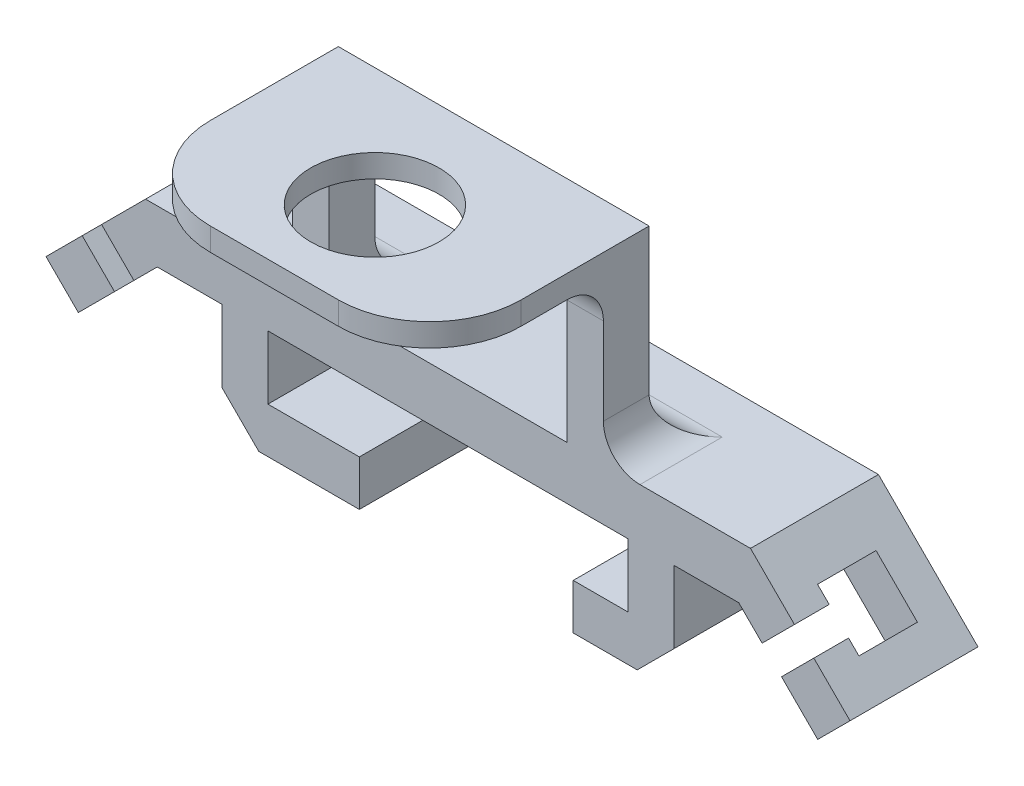
SolidWorks part; units mm, degrees
ref_plane "Front Plane" through (0, 0, 0) normal (0, 0, 1) x (1, 0, 0)
ref_plane "Top Plane" through (0, 0, 0) normal (0, 1, 0) x (1, 0, 0)
ref_plane "Right Plane" through (0, 0, 0) normal (1, 0, 0) x (0, 0, -1)
sketch "Sketch2" plane through (0, 0, 0) normal (0, 0, 1) x (1, 0, 0)
  line L0 (15.9053, 19.45) -> (-15.9053, 19.45)
  line L1 (16.5463, 22.3446) -> (-16.5463, 22.3446)
  line L2 (15.9053, 19.45) -> (20.2233, 15.1321)
  line L5 (20.2233, 15.1321) -> (21.991, 16.8999)
  line L6 (16.5463, 22.3446) -> (21.991, 16.8999)
  line L7 (-20.2233, 15.1321) -> (-21.991, 16.8999)
  line L8 (-15.9053, 19.45) -> (-20.2233, 15.1321)
  line L10 (-16.5463, 22.3446) -> (-21.991, 16.8999)
  dimension "D1" = 2.5
  dimension "D2" = 2.5
extrude "Boss-Extrude2" add sketch "Sketch2" along normal blind 5
extrude "Boss-Extrude3" add sketch "Sketch2<2>" against normal blind 2
sketch "Sketch2<2>" plane through (0, 0, 0) normal (0, 0, 1) x (1, 0, 0) same geometry as "Sketch2"
ref_plane "Plane1" through (19.4454, 19.4454, 0) normal (0.7071, 0.7071, 0) x (0.7071, -0.7071, 0)
sketch "Sketch4" plane through (19.4454, 19.4454, 0) normal (0.7071, 0.7071, 0) x (0.7071, -0.7071, 0)
  line L6 (1.6, -3.1) -> (-1.6, -3.1)
  line L7 (1.6, -3.1) -> (1.6, 0.1)
  line L8 (1.6, 0.1) -> (-1.6, 0.1)
  line L9 (-1.6, -3.1) -> (-1.6, 0.1)
  dimension "D1" = 3.2
extrude "Cut-Extrude1" cut sketch "Sketch4" against normal blind 2.5
ref_plane "Plane2" through (-19.4454, 19.4454, 0) normal (-0.7071, 0.7071, 0) x (0, 0, 1)
sketch "Sketch5" plane through (-19.4454, 19.4454, 0) normal (-0.7071, 0.7071, 0) x (0, 0, 1)
  line L5 (3.1, 1.6) -> (-0.1, 1.6)
  line L6 (3.1, 1.6) -> (3.1, -1.6)
  line L7 (3.1, -1.6) -> (-0.1, -1.6)
  line L8 (-0.1, 1.6) -> (-0.1, -1.6)
  dimension "D1" = 3.2
extrude "Cut-Extrude2" cut sketch "Sketch5" against normal blind 2.5
ref_plane "Plane4" through (0, 0, 5) normal (0, 0, 1) x (1, 0, 0)
sketch "Sketch6" plane through (0, 0, 5) normal (0, 0, 1) x (1, 0, 0)
  line L0 (-20.0111, 18.8798) -> (-18.9505, 19.9404)
  line L1 (-20.0111, 18.8798) -> (-18.2434, 17.112)
  line L2 (-18.9505, 19.9404) -> (-17.1827, 18.1726)
  line L3 (-18.2434, 17.112) -> (-17.1827, 18.1726)
  line L4 (-16.7231, 22.1678) -> (-22.1678, 16.7231) construction
  line L5 (-21.991, 16.8999) -> (-20.2233, 15.1321) construction
  dimension "D1" = 2.8
  dimension "D2" = 1.5
  dimension "D3" = 2.5
extrude "Cut-Extrude4" cut sketch "Sketch6" against normal up to next
sketch "Sketch7" plane through (0, 0, 5) normal (0, 0, 1) x (1, 0, 0)
  line L0 (17.1827, 18.1726) -> (18.9505, 19.9404)
  line L1 (15.9053, 19.45) -> (20.2233, 15.1321) construction
  line L2 (21.991, 16.8999) -> (16.5463, 22.3446) construction
  line L3 (18.9505, 19.9404) -> (20.0111, 18.8798)
  line L7 (20.0111, 18.8798) -> (18.2434, 17.112)
  line L8 (18.2434, 17.112) -> (17.1827, 18.1726)
  line L9 (20.2233, 15.1321) -> (21.991, 16.8999) construction
  dimension "D1" = 2.8
  dimension "D2" = 1.5
  dimension "D3" = 2.5
extrude "Cut-Extrude5" cut sketch "Sketch7" against normal up to next
ref_plane "Plane6" through (0, 19.45, 0) normal (0, -1, 0) x (-1, 0, 0)
sketch "Sketch8" plane through (0, 19.45, 0) normal (0, -1, 0) x (-1, 0, 0)
  line L1 (-2.2946, -5) -> (2.2946, -5) construction
  line L2 (12.35, 2) -> (9.85, 2)
  line L3 (15.9053, 2) -> (-15.9053, 2) construction
  line L4 (-9.85, 2) -> (-9.85, -5)
  line L5 (-9.85, -5) -> (-12.35, -5)
  line L6 (-12.35, -5) -> (-12.35, 2)
  line L7 (-12.35, 2) -> (-9.85, 2)
  line L8 (12.35, -5) -> (12.35, 2)
  line L9 (9.85, -5) -> (12.35, -5)
  line L10 (9.85, 2) -> (9.85, -5)
  point P0 (0, 0)
  dimension "D1" = 9.85
  dimension "D2" = 9.85
  dimension "D3" = 2.5
  dimension "D4" = 2.5
extrude "Boss-Extrude4" add sketch "Sketch8" along normal blind 5.96
ref_plane "Plane7" through (9.85, 0, 0) normal (-1, 0, 0) x (0, 0, 1)
sketch "Sketch10" plane through (9.85, 0, 0) normal (-1, 0, 0) x (0, 0, 1)
  line L0 (5, 13.49) -> (-2, 13.49) construction
  line L1 (5, 13.49) -> (-2, 13.49)
  line L2 (5, 13.49) -> (5, 15.98)
  line L3 (5, 15.98) -> (-2, 15.98)
  line L4 (-2, 13.49) -> (-2, 15.98)
  line L5 (-2, 13.49) -> (-2, 19.45) construction
  dimension "D1" = 2.49
extrude "Boss-Extrude5" add sketch "Sketch10" along normal blind 3
ref_plane "Plane8" through (-9.85, 0, 0) normal (1, 0, 0) x (0, 0, -1)
sketch "Sketch11" plane through (-9.85, 0, 0) normal (1, 0, 0) x (0, 0, -1)
  line L0 (2, 13.49) -> (2, 19.45) construction
  line L1 (-5, 13.49) -> (2, 13.49)
  line L2 (-5, 13.49) -> (-5, 15.98)
  line L3 (-5, 15.98) -> (2, 15.98)
  line L4 (2, 13.49) -> (2, 15.98)
  dimension "D1" = 2.49
extrude "Boss-Extrude6" add sketch "Sketch11" along normal blind 5
ref_plane "Plane9" through (0, 22.3446, 0) normal (0, 1, 0) x (1, 0, 0)
sketch "Sketch12" plane through (0, 22.3446, 0) normal (0, 1, 0) x (1, 0, 0)
  line L3 (16.5463, -5) -> (-16.5463, -5) construction
  line L4 (8.5, -5) -> (-8.5, -5)
  line L5 (8.5, -5) -> (8.5, -2.5)
  line L6 (8.5, -2.5) -> (-8.5, -2.5)
  line L7 (-8.5, -5) -> (-8.5, -2.5)
  point P6 (0, 0)
  dimension "D1" = 17
  dimension "D2" = 8.5
  dimension "D3" = 2.5
extrude "Boss-Extrude7" add sketch "Sketch12" along normal blind 10
ref_plane "Plane10" through (0, 0, 5) normal (0, 0, 1) x (1, 0, 0)
sketch "Sketch14" plane through (0, 0, 5) normal (0, 0, 1) x (1, 0, 0)
  line L0 (-8.5, 32.3446) -> (8.5, 32.3446) construction
  line L2 (-8.5, 22.3446) -> (-16.5463, 22.3446) construction
  line L7 (-6.5, 31.0946) -> (6.5, 31.0946)
  line L8 (-6.5, 31.0946) -> (-6.5, 22.3446)
  line L9 (-6.5, 22.3446) -> (6.5, 22.3446)
  line L10 (6.5, 31.0946) -> (6.5, 22.3446)
  dimension "D1" = 1.25
  dimension "D2" = 0
extrude "Cut-Extrude7" cut sketch "Sketch14" against normal up to next
sketch "Sketch16" plane through (0, 0, 5) normal (0, 0, 1) x (1, 0, 0)
  line L0 (8.5, 32.3446) -> (8.5, 22.3446) construction
  line L1 (-8.5, 32.3446) -> (8.5, 32.3446)
  line L2 (-8.5, 32.3446) -> (-8.5, 31.0946)
  line L3 (-8.5, 31.0946) -> (8.5, 31.0946)
  line L4 (8.5, 32.3446) -> (8.5, 31.0946)
  dimension "D1" = 1.25
extrude "Boss-Extrude8" add sketch "Sketch16" along normal blind 9.5
ref_plane "Plane11" through (0, 32.3446, 0) normal (0, 1, 0) x (1, 0, 0)
sketch "Sketch17" plane through (0, 32.3446, 0) normal (0, 1, 0) x (1, 0, 0)
  line L0 (8.5, -14.5) -> (-8.5, -14.5) construction
  line L1 (-8.5, -2.5) -> (-8.5, -14.5) construction
  circle A0 centre (0, -9) radius 3.51
  dimension "D1" = 5.5
  dimension "D2" = 8.5
extrude "Cut-Extrude8" cut sketch "Sketch17" against normal up to next
fillet "Fillet7" radius 2 1 edges at (7.5, 31.0946, 5)
fillet "Fillet8" radius 5 1 edges at (8.5, 31.7196, 14.5)
fillet "Fillet9" radius 5 1 edges at (-8.5, 31.7196, 14.5)
chamfer "Chamfer1" distance 2 angle 45 1 edges at (-12.35, 13.49, 1.5)
chamfer "Chamfer2" distance 2 angle 45 1 edges at (12.35, 13.49, 1.5)
ref_plane "Plane13" through (0, 0, 2.5) normal (0, 0, -1) x (-1, 0, 0)
sketch "Sketch22" plane through (0, 0, 2.5) normal (0, 0, -1) x (-1, 0, 0)
  line L1 (6.5, 22.3446) -> (8.5, 22.3446)
  line L2 (6.5, 22.3446) -> (6.5, 32.3446)
  line L3 (6.5, 32.3446) -> (8.5, 32.3446)
  line L4 (8.5, 22.3446) -> (8.5, 32.3446)
  line L5 (-6.5, 22.3446) -> (-8.5, 22.3446)
  line L6 (-6.5, 22.3446) -> (-6.5, 32.3446)
  line L7 (-6.5, 32.3446) -> (-8.5, 32.3446)
  line L8 (-8.5, 22.3446) -> (-8.5, 32.3446)
ref_plane "Plane14" through (-8.5, 0, 0) normal (-1, 0, 0) x (0, 0, 1)
fillet "Fillet11" radius 2 1 edges
fillet "Fillet12" radius 2 1 edges
fillet "Fillet13" radius 2 1 edges at (8.5, 22.3446, 2.5)
fillet "Fillet14" radius 2 1 edges at (-8.5, 22.3446, 2.5)
fillet "Fillet16" radius 2 1 edges at (-7.5, 31.0946, 5)
